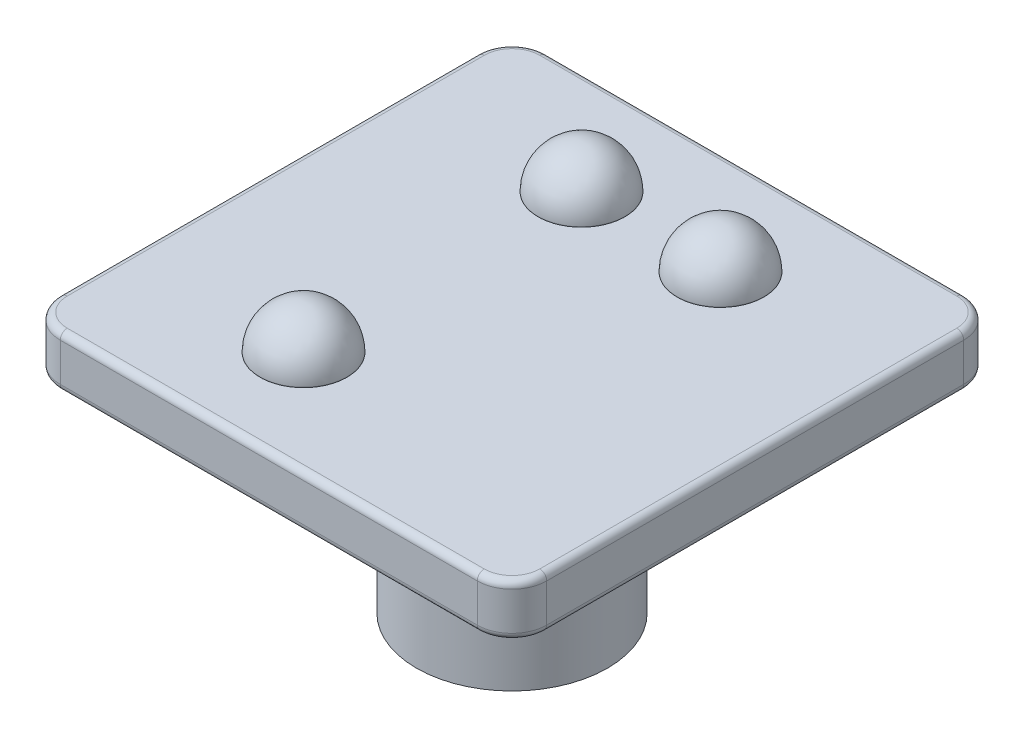
SolidWorks part; units mm, degrees
ref_plane "Front Plane" through (0, 0, 0) normal (0, 0, 1) x (1, 0, 0)
ref_plane "Top Plane" through (0, 0, 0) normal (0, 1, 0) x (1, 0, 0)
ref_plane "Right Plane" through (0, 0, 0) normal (1, 0, 0) x (0, 0, -1)
sketch "Sketch1" plane through (0, 0, 0) normal (0, 1, 0) x (1, 0, 0)
  line L1 (-7.3247, 4.3967) -> (4.6753, 4.3967)
  line L2 (-8.3247, 3.3967) -> (-8.3247, -8.6033)
  line L3 (-7.3247, -9.6033) -> (4.6753, -9.6033)
  line L4 (5.6753, 3.3967) -> (5.6753, -8.6033)
  arc A0 (-8.3247, -8.6033) -> (-7.3247, -9.6033) centre (-7.3247, -8.6033) ccw
  arc A1 (4.6753, -9.6033) -> (5.6753, -8.6033) centre (4.6753, -8.6033) ccw
  arc A2 (4.6753, 4.3967) -> (5.6753, 3.3967) centre (4.6753, 3.3967) cw
  arc A3 (-7.3247, 4.3967) -> (-8.3247, 3.3967) centre (-7.3247, 3.3967) ccw
  point P8 (5.6753, -9.6033)
  point P11 (5.6753, 4.3967)
  point P14 (-8.3247, 4.3967)
  dimension "D3" = 1
  dimension "D1" = 14
  dimension "D2" = 14
extrude "Boss-Extrude1" add sketch "Sketch1" along normal blind 1.5
sketch "Sketch2" plane through (0, 0, 0) normal (0, -1, 0) x (1, 0, 0)
  line L0 (-7.3247, 9.6033) -> (4.6753, 9.6033) construction
  line L1 (5.6753, 8.6033) -> (5.6753, -3.3967) construction
  line L2 (-1.3247, -4.3967) -> (-1.3247, 9.6033) construction
  line L3 (-8.3247, 2.6033) -> (5.6753, 2.6033) construction
  line L4 (-8.3247, -3.3967) -> (-8.3247, 8.6033) construction
  circle A0 centre (-1.3247, 2.6033) radius 2.75
  dimension "D1" = 7
  dimension "D2" = 7
extrude "Boss-Extrude2" add sketch "Sketch2" along normal blind 6
sketch "Sketch3" plane through (0, -6, 0) normal (0, -1, 0) x (1, 0, 0)
  line L0 (-1.3247, 5.3533) -> (-1.3247, -0.1467) construction
  line L1 (-3.3247, 3.1533) -> (0.6753, 3.1533)
  line L2 (-3.3247, 3.1533) -> (-3.3247, 2.0533)
  line L3 (-3.3247, 2.0533) -> (0.6753, 2.0533)
  line L4 (0.6753, 3.1533) -> (0.6753, 2.0533)
  line L5 (-1.8747, 4.6033) -> (-0.7747, 4.6033)
  line L6 (-1.8747, 4.6033) -> (-1.8747, 0.6033)
  line L7 (-1.8747, 0.6033) -> (-0.7747, 0.6033)
  line L8 (-0.7747, 4.6033) -> (-0.7747, 0.6033)
  line L9 (-4.0747, 2.6033) -> (1.4253, 2.6033) construction
  circle A3 centre (-1.3247, 2.6033) radius 2.75 construction
  circle A4 centre (-1.3247, 2.6033) radius 2.75 construction
  dimension "D7" = 0.55
  dimension "D1" = 4
  dimension "D2" = 1.1
  dimension "D3" = 1.1
  dimension "D4" = 4
  dimension "D8" = 0.55
extrude "Cut-Extrude1" cut sketch "Sketch3" against normal blind 6 contours L8 L5 L6 L1 | L1 L8 L3 L4 | L8 L1 L6 L3 | L6 L1 L2 L3 | L8 L3 L6 L7 region at (-2.5997, -6, 2.6033) region at (-1.3247, -6, 3.8783) region at (-1.3247, -6, 2.6033) region at (-0.0497, -6, 2.6033) region at (-1.3247, -6, 1.3283)
chamfer "Chamfer1" distance 0.3 angle 45 12 edges at (-1.3247, -6, 0.6033) (-1.8747, -6, 1.3283) (-2.5997, -6, 2.0533) (-3.3247, -6, 2.6033) (-2.5997, -6, 3.1533) (-0.7747, -6, 1.3283) (-0.0497, -6, 2.0533) (0.6753, -6, 2.6033) (-0.0497, -6, 3.1533) (-0.7747, -6, 3.8783) (-1.3247, -6, 4.6033) (-1.8747, -6, 3.8783)
fillet "Fillet1" radius 1 1 edges at (-1.3247, 0, -0.1467)
sketch "Sketch4" plane through (0, 1.5, 0) normal (0, 1, 0) x (1, 0, 0)
  line L0 (-1.3247, 4.3967) -> (-1.3247, -9.6033) construction
  line L1 (4.6753, 4.3967) -> (-7.3247, 4.3967) construction
  line L2 (-7.3247, -9.6033) -> (4.6753, -9.6033) construction
  line L3 (5.6753, -2.6033) -> (-8.3247, -2.6033) construction
  line L4 (-8.3247, 3.3967) -> (-8.3247, -8.6033) construction
  line L5 (5.6753, -8.6033) -> (5.6753, 3.3967) construction
  line L6 (-3.3247, 4.3967) -> (-3.3247, -9.6033) construction
  line L7 (0.6753, 4.3967) -> (0.6753, -9.6033) construction
  line L8 (-8.3247, 1.3967) -> (5.6753, 1.3967) construction
  line L9 (5.6753, -6.6033) -> (-8.3247, -6.6033) construction
  circle A0 centre (-3.3247, 1.3967) radius 1.25
  circle A3 centre (-3.3247, -6.6033) radius 1.25
  circle A5 centre (0.6753, 1.3967) radius 1.25
  dimension "D1" = 4
  dimension "D2" = 4
  dimension "D3" = 2
  dimension "D4" = 2
extrude "Boss-Extrude3" add sketch "Sketch4" along normal blind 0.01
dome "Dome1" faces to dome 1 distance 1.25 reverse direction no elliptical dome no face at (-3.3247, 1.51, -0.1467) parameters "D1"=1.25
dome "Dome2" faces to dome 1 distance 1.25 reverse direction no elliptical dome no face at (0.6753, 1.51, -0.1467) parameters "D1"=1.25
dome "Dome5" faces to dome 1 distance 1.25 reverse direction no elliptical dome no face at (-3.3247, 1.51, 7.8533) parameters "D1"=1.25
fillet "Fillet3" radius 0.2 16 edges at (5.3824, 1.5, -4.1038) (5.6753, 1.5, 2.6033) (5.3824, 1.5, 9.3104) (-1.3247, 1.5, 9.6033) (-8.0318, 1.5, 9.3104) (-8.0318, 1.5, -4.1038) (-8.3247, 1.5, 2.6033) (-1.3247, 1.5, -4.3967) (5.3824, 0, 9.3104) (5.6753, 0, 2.6033) (5.3824, 0, -4.1038) (-1.3247, 0, -4.3967) (-8.0318, 0, -4.1038) (-8.3247, 0, 2.6033) (-8.0318, 0, 9.3104) (-1.3247, 0, 9.6033)
